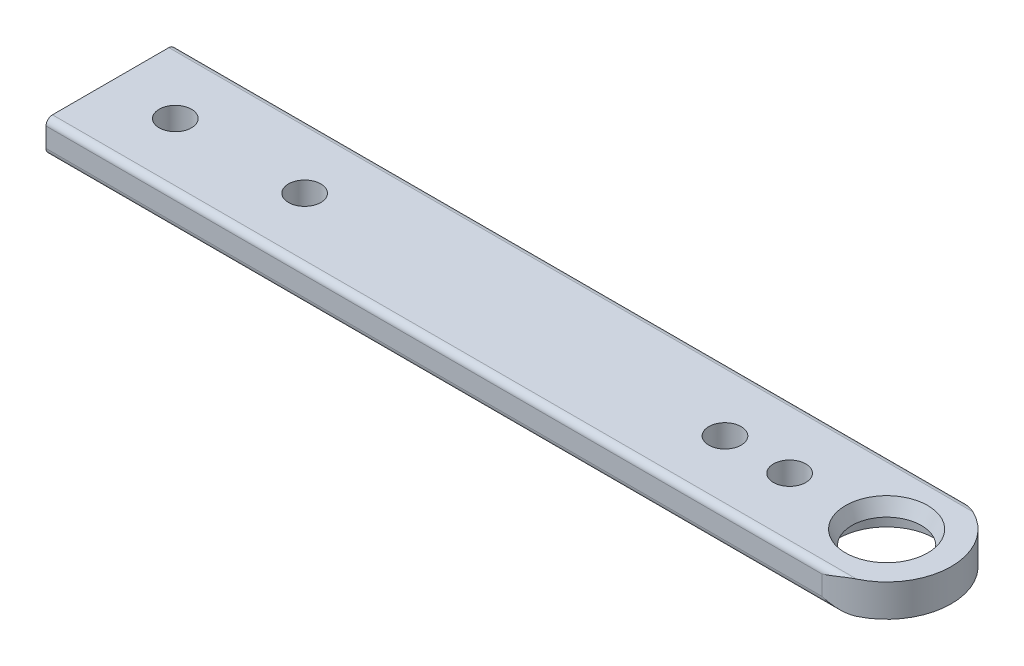
SolidWorks part; units mm, degrees
material "Plain Carbon Steel"
ref_plane "Front Plane" through (0, 0, 0) normal (0, 0, 1) x (1, 0, 0)
ref_plane "Top Plane" through (0, 0, 0) normal (0, 1, 0) x (1, 0, 0)
ref_plane "Right Plane" through (0, 0, 0) normal (1, 0, 0) x (0, 0, -1)
sketch "Sketch1" plane through (0, 0, 0) normal (0, 1, 0) x (1, 0, 0)
  line L1 (82.55, -12.7) -> (-82.55, -12.7)
  line L2 (82.55, -12.7) -> (82.55, 12.7)
  line L3 (82.55, 12.7) -> (-82.55, 12.7)
  line L4 (-82.55, -12.7) -> (-82.55, 12.7)
  line L5 (82.55, -12.7) -> (-82.55, 12.7) construction
  line L6 (82.55, 12.7) -> (-82.55, -12.7) construction
  point P0 (0, 0)
  dimension "D1" = 25.4
  dimension "D2" = 165.1
extrude "Boss-Extrude1" add sketch "Sketch1" along normal blind 6.35
fillet "Fillet1" radius 1.27 4 edges at (0, 0, -12.7) (0, 6.35, -12.7) (0, 0, 12.7) (0, 6.35, 12.7)
sketch "Sketch2" plane through (0, 6.35, 0) normal (0, 1, 0) x (1, 0, 0)
  line L0 (-82.55, 0) -> (82.55, 0) construction
  line L1 (-82.55, 11.43) -> (-82.55, -11.43) construction
  line L2 (82.55, -11.43) -> (82.55, 11.43) construction
  circle A0 centre (-69.85, 0) radius 3.175
  circle A3 centre (69.85, 0) radius 6.35
  circle A7 centre (-44.45, 0) radius 3.175
  line M13 (82.55, 11.43) -> (-82.55, 11.43)
  line M15 (-82.55, -11.43) -> (82.55, -11.43)
  dimension "D1" = 12.7
  dimension "D4" = 6.35
  dimension "D2" = 139.7
  dimension "D3" = 12.7
  dimension "D5" = 2
extrude "Cut-Extrude1" cut sketch "Sketch2" against normal through all contours M13 | M15 | A0 L0 | L0 A3 | A3 L0 | A0 | A7 region at (-69.85, 6.35, -1.3475) region at (69.85, 6.35, -2.695) region at (69.85, 6.35, 2.695)
sketch "Sketch3" plane through (0, 0, 0) normal (0, -1, 0) x (1, 0, 0)
  circle A0 centre (69.85, 0) radius 9.525
  dimension "D1" = 19.05
extrude "Cut-Extrude2" cut sketch "Sketch3" against normal blind 3.5719
sketch "Sketch4" plane through (0, 0, 0) normal (0, -1, 0) x (1, 0, 0)
  line L1 (57.15, -12.7) -> (82.55, -12.7)
  line L2 (57.15, -12.7) -> (57.15, 12.7)
  line L3 (57.15, 12.7) -> (82.55, 12.7)
  line L4 (82.55, -12.7) -> (82.55, 12.7)
  line L5 (57.15, -12.7) -> (82.55, 12.7) construction
  line L6 (57.15, 12.7) -> (82.55, -12.7) construction
  circle A0 centre (69.85, 0) radius 12.7
  point P0 (69.85, 0)
  line M9 (-82.55, -11.43) -> (82.55, -11.43)
  line M10 (82.55, -11.43) -> (82.55, 11.43)
  line M11 (82.55, 11.43) -> (-82.55, 11.43)
extrude "Cut-Extrude3" cut sketch "Sketch4" against normal through all contours A0 L4 L3 M11 | A0 L4 M11 | A0 M9 M10 | A0 L1 L4 M9 region at (77.9706, 0, -12.1169) region at (80.5682, 0, -8.7575) region at (80.5682, 0, 8.7575) region at (77.9706, 0, 12.1169)
sketch "Sketch5" plane through (0, 0, 0) normal (0, -1, 0) x (1, 0, 0)
  line L0 (-82.55, 0) -> (82.55, 0) construction
  circle A0 centre (50.8, 0) radius 3.175
  circle A1 centre (38.1, 0) radius 3.175
  dimension "D1" = 6.35
  dimension "D2" = 12.7
  dimension "D3" = 19.05
extrude "Cut-Extrude4" cut sketch "Sketch5" against normal through all
ref_axis "Axis1" through (69.85, 3.5719, 0) along (0, 1, 0)
ref_plane "Plane2" through (0, 0, 0) normal (0, 0, 1) x (1, 0, 0)
sketch "Sketch8" plane through (0, 0, 0) normal (0, 0, 1) x (1, 0, 0)
  line L1 (69.85, 6.35) -> (69.85, 0)
  line L3 (69.85, 3.5719) -> (69.85, 6.35) construction
  line L12 (-82.55, 6.35) -> (75.3858, 6.35) construction
  line L13 (75.3858, 0) -> (-82.55, 0) construction
  line L14 (69.85, 0) -> (73.5442, 8.2974)
  line L15 (73.5442, 8.2974) -> (77.9182, 6.35)
  line L16 (77.9182, 6.35) -> (74.224, -1.9474)
  line L17 (74.224, -1.9474) -> (69.85, 0)
  line L18 (82.55, 6.35) -> (75.3858, 6.35) construction
  line L19 (69.85, 6.35) -> (76.2, 6.35)
  line L36 (76.2, 6.35) -> (76.2, 3.5719)
  line L37 (76.2, 3.5719) -> (69.85, 3.5719)
  line L38 (76.2, 6.35) -> (77.9182, 6.35)
  line L39 (76.2, 3.5719) -> (76.6813, 3.5719)
  dimension "D1" = 24
  dimension "D2" = 4.7879
  dimension "D3" = 6.35
  dimension "D4" = 2.7781
revolve "Cut-Revolve1" cut sketch "Sketch8" angle 360 about axis through (69.85, 3.5719, 0) along (0, 1, 0) region at (76.8078, 5.2213, 0)
